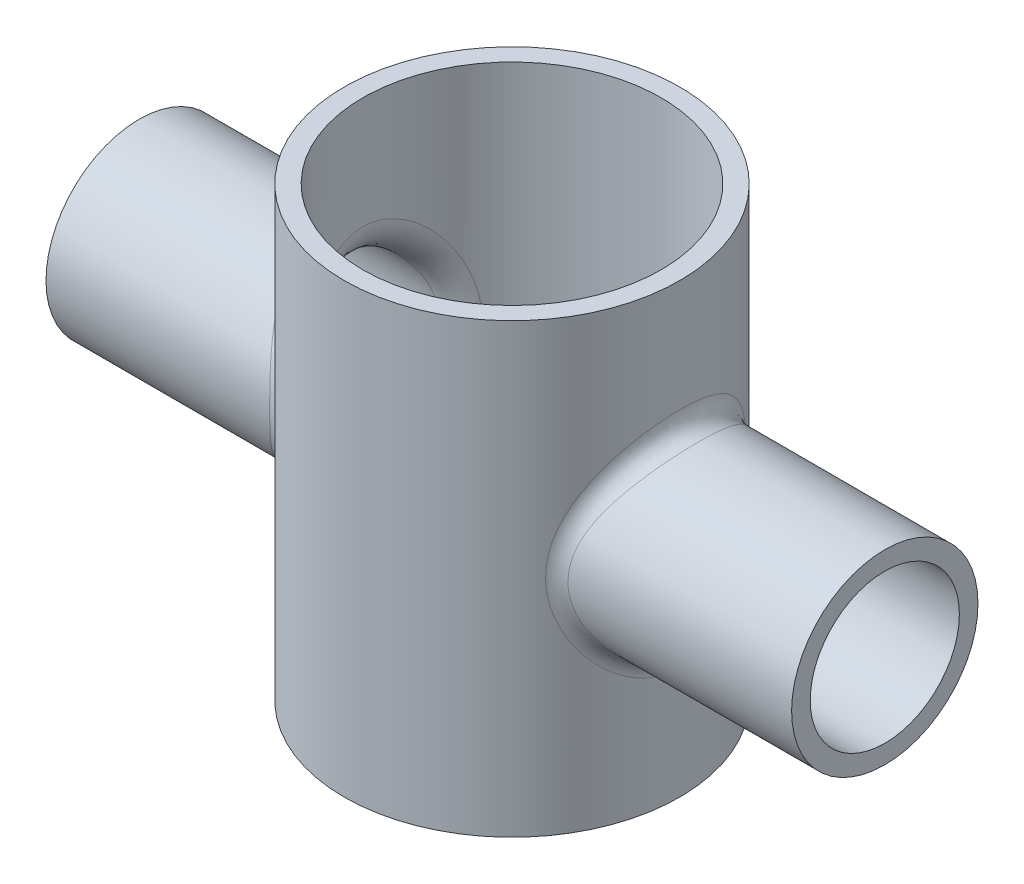
SolidWorks part; units mm, degrees
material "1345 Alloy"
ref_plane "Front Plane" through (0, 0, 0) normal (0, 0, 1) x (1, 0, 0)
ref_plane "Top Plane" through (0, 0, 0) normal (0, 1, 0) x (1, 0, 0)
ref_plane "Right Plane" through (0, 0, 0) normal (1, 0, 0) x (0, 0, -1)
sketch "Sketch1" plane through (0, 0, 0) normal (0, 1, 0) x (1, 0, 0)
  circle A0 centre (0, 0) radius 45
  dimension "D1" = 90
extrude "Boss-Extrude1" add sketch "Sketch1" along normal mid plane 120
sketch "Sketch2" plane through (0, 0, 0) normal (1, 0, 0) x (0, 0, -1)
  circle A0 centre (0, 0) radius 25
  dimension "D1" = 50
extrude "Boss-Extrude2" add sketch "Sketch2" along normal mid plane 200
fillet "Fillet1" radius 5 2 edges at (-37.4736, -2.0661, -24.9145) (37.4736, 2.0661, -24.9145)
shell "Shell1" thickness 5 removed face at (-100, 0, -25) removed face at (100, 0, -25) removed face at (0, 60, 45)
equation "\"CENTRAL_WIDTH\"= 80 + 10"
equation "\"D1@Sketch1\"=\"CENTRAL_WIDTH\""
equation "\"D1@Sketch2\"=\"CENTRAL_WIDTH\"*50/90"
equation "\"D1@Boss-Extrude2\"=\"CENTRAL_WIDTH\"*200/90"
